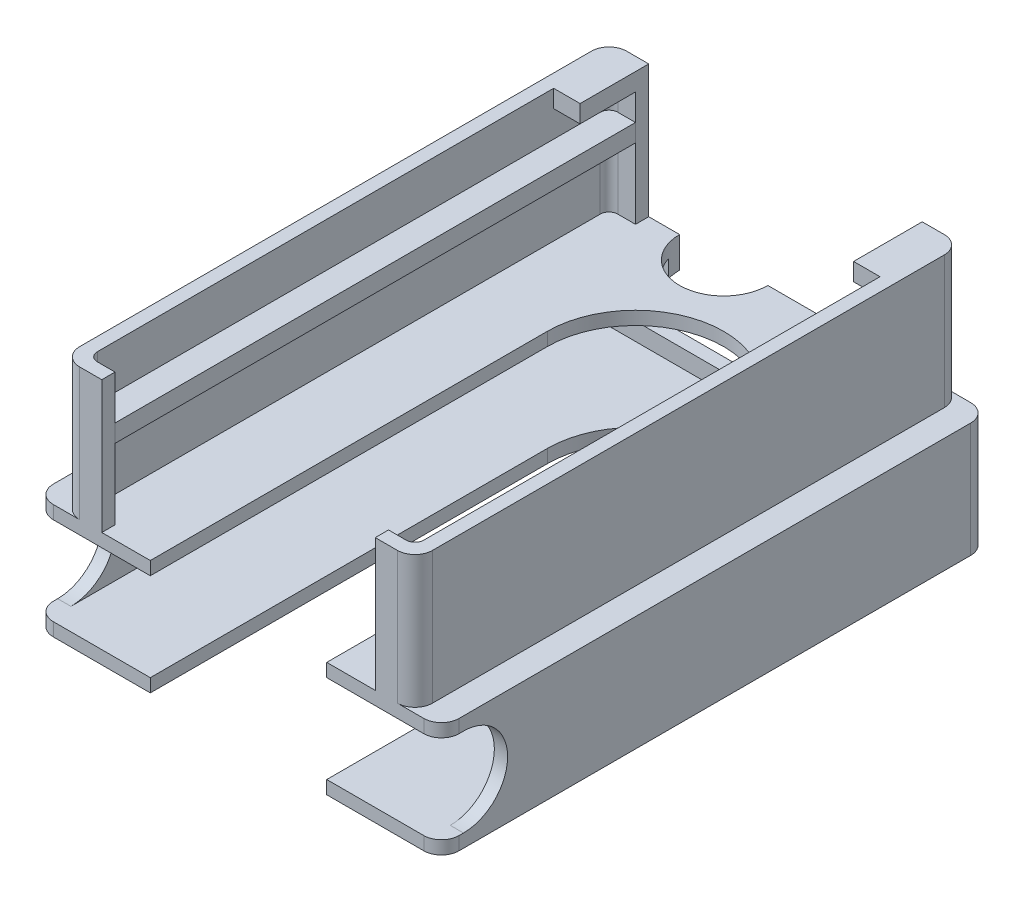
SolidWorks part; units mm, degrees
ref_plane "Front Plane" through (0, 0, 0) normal (0, 0, 1) x (1, 0, 0)
ref_plane "Top Plane" through (0, 0, 0) normal (0, 1, 0) x (1, 0, 0)
ref_plane "Right Plane" through (0, 0, 0) normal (1, 0, 0) x (0, 0, -1)
sketch "battery-base" plane through (0, 0, 0) normal (0, 1, 0) x (1, 0, 0)
  line L0 (-10.75, -13.5) -> (-11.5, -13.5)
  line L1 (-10.5, 16.25) -> (10.5, 16.25)
  line L2 (11.5, 15.25) -> (11.5, -13.75)
  line L3 (10.5, -14.75) -> (-10.5, -14.75)
  line L4 (-11.5, 15.25) -> (-11.5, -13.75)
  line L7 (10.25, 15.5) -> (-10.25, 15.5)
  line L8 (10.75, 15) -> (10.75, -13.5)
  line L9 (10.25, -14) -> (-10.25, -14)
  line L10 (-10.75, 15) -> (-10.75, -13.5)
  line L13 (10.75, -13.5) -> (11.5, -13.5)
  arc A0 (-11.5, -13.75) -> (-10.5, -14.75) centre (-10.5, -13.75) ccw
  arc A1 (11.5, -13.75) -> (10.5, -14.75) centre (10.5, -13.75) cw
  arc A2 (11.5, 15.25) -> (10.5, 16.25) centre (10.5, 15.25) ccw
  arc A3 (-11.5, 15.25) -> (-10.5, 16.25) centre (-10.5, 15.25) cw
  arc A4 (-10.75, 15) -> (-10.25, 15.5) centre (-10.25, 15) cw
  arc A5 (-10.75, -13.5) -> (-10.25, -14) centre (-10.25, -13.5) ccw
  arc A6 (10.25, -14) -> (10.75, -13.5) centre (10.25, -13.5) ccw
  arc A7 (10.75, 15) -> (10.25, 15.5) centre (10.25, 15) ccw
  point P0 (0, 0)
  point P6 (0, 0)
extrude "base-extrude" add sketch "battery-base" along normal blind 0.75 contours L3 A0 L4 A3 L1 A2 L2 A1
extrude "sidewall-extrude" add sketch "battery-base<12>" along normal blind 5.75 contours A7 L8 L13 L2 A2 L1 A3 L4 L0 L10 A4 L7 region at (-11.125, 0, 13.124)
sketch "battery-base<12>" plane through (0, 0, 0) normal (0, 1, 0) x (1, 0, 0) same geometry as "battery-base"
extrude "top-extrude" add sketch "battery-base<13>" along normal blind 0.75 from offset 5.75 contours L8 A7 L7 A4 L10 A5 L9 A6 | A6 L9 A5 L0 L4 A0 L3 A1 L2 L13 | A7 L8 L13 L2 A2 L1 A3 L4 L0 L10 A4 L7 region at (0, 0, 14.3418) region at (-11.125, 0, 13.124) region at (0, 0, -0.75)
sketch "battery-base<13>" plane through (0, 0, 0) normal (0, 1, 0) x (1, 0, 0) same geometry as "battery-base"
sketch "round-cut" plane through (11.5, 0, 0) normal (1, 0, 0) x (0, 0, -1)
  line L0 (-13.5, 5.75) -> (-13.5, 0.75) construction
  line L1 (-13.5, 5.75) -> (-13.75, 5.75) construction
  arc A0 (-13.5, 0.75) -> (-13.5, 5.75) centre (-13.5, 3.25) ccw
extrude "Cut-Extrude1" cut sketch "round-cut" against normal through all and the other way through all
sketch "PCB-support" plane through (0, 6.5, 0) normal (0, 1, 0) x (1, 0, 0)
  line L0 (-7.75, -14) -> (-7.75, 15.5)
  line L1 (-8.75, 15.5) -> (8.75, 15.5)
  line L2 (-9.25, 15) -> (-9.25, -13.5)
  line L3 (-8.75, -14) -> (8.75, -14)
  line L4 (9.25, 15) -> (9.25, -13.5)
  line L5 (-9, 16.25) -> (9, 16.25)
  line L6 (-10, 15.25) -> (-10, -13.75)
  line L7 (-9, -14.75) -> (9, -14.75)
  line L8 (10, 15.25) -> (10, -13.75)
  line L9 (7.75, -14) -> (7.75, 15.5)
  line L10 (-7.75, -14) -> (-7.75, -14.75)
  line L11 (7.75, -14) -> (7.75, -14.75)
  line L12 (-7.75, 15.5) -> (-7.75, 16.25)
  line L13 (7.75, 15.5) -> (7.75, 16.25)
  line L14 (-9.25, 12.3596) -> (-7.75, 12.3596)
  line L15 (-7.75, 12.3596) -> (7.75, 12.3596)
  line L16 (7.75, 12.3596) -> (9.25, 12.3596)
  arc A0 (-10, -13.75) -> (-9, -14.75) centre (-9, -13.75) ccw
  arc A1 (9, -14.75) -> (10, -13.75) centre (9, -13.75) ccw
  arc A2 (10, 15.25) -> (9, 16.25) centre (9, 15.25) ccw
  arc A3 (-9, 16.25) -> (-10, 15.25) centre (-9, 15.25) ccw
  arc A4 (-9.25, -13.5) -> (-8.75, -14) centre (-8.75, -13.5) ccw
  arc A5 (8.75, -14) -> (9.25, -13.5) centre (8.75, -13.5) ccw
  arc A6 (9.25, 15) -> (8.75, 15.5) centre (8.75, 15) ccw
  arc A7 (-8.75, 15.5) -> (-9.25, 15) centre (-8.75, 15) ccw
  line M4 (-10.5, -14.75) -> (10.5, -14.75)
  line M8 (10.5, 16.25) -> (-10.5, 16.25)
extrude "PCB-support-extrude" add sketch "PCB-support" along normal blind 1 from offset 4 contours L1 A7 L2 A4 L3 L0 | L4 A6 L1 L9 L3 A5 | L1 A7 L2 L14 L0 | L4 A6 L1 L9 L16 region at (-8.4991, 6.5, 0.8024) region at (-8.4926, 6.5, -13.913) region at (8.4991, 6.5, 0.8024) region at (8.4926, 6.5, -13.913)
extrude "PCB-rim-extrude" add sketch "PCB-support<3>" along normal blind 7.5 contours A7 L1 A6 L4 A5 L3 L11 A1 L8 A2 A3 L6 A0 L10 A4 L2 M4 M8 | A7 L1 L12 L5 A3 L6 A0 L10 L3 A4 L2 M4 region at (-9.5198, 6.5, -0.75) region at (9.5198, 6.5, -0.75)
sketch "PCB-support<3>" plane through (0, 6.5, 0) normal (0, 1, 0) x (1, 0, 0) same geometry as "PCB-support"
sketch "cut-away" plane through (0, 6.5, 0) normal (0, 1, 0) x (1, 0, 0)
  line L0 (-5, 7.75) -> (-5, -14.75)
  line L2 (5, 7.75) -> (5, -14.75)
  line L3 (5, -14.75) -> (-5, -14.75)
  line L4 (7.75, -14.75) -> (-7.75, -14.75) construction
  arc A0 (-5, 7.75) -> (5, 7.75) centre (0, 7.75) cw
extrude "Cut-Extrude2" cut sketch "cut-away" against normal through all
sketch "Sketch7" plane through (0, 0, -16.25) normal (0, 0, -1) x (-1, 0, 0)
  line L0 (8.5849, 3.25) -> (-8.5849, 3.25) construction
  line L1 (8.5849, 1.75) -> (-8.5849, 1.75)
  line L2 (8.5849, 4.75) -> (-8.5849, 4.75)
  arc A0 (8.5849, 1.75) -> (8.5849, 4.75) centre (8.5849, 3.25) ccw
  arc A1 (-8.5849, 4.75) -> (-8.5849, 1.75) centre (-8.5849, 3.25) ccw
  point P2 (0, 3.25)
extrude "Cut-Extrude3" cut sketch "Sketch7" against normal blind 3.5
sketch "Sketch8" plane through (0, 6.5, 0) normal (0, 1, 0) x (1, 0, 0)
  line L1 (-6, 16.25) -> (-1, 16.25)
  line L2 (-7.75, 16.25) -> (7.75, 16.25) construction
  arc A0 (-6, 16.25) -> (-1, 16.25) centre (-3.5, 16.25) ccw
extrude "Cut-Extrude4" cut sketch "Sketch8" against normal blind 2
extrude "Boss-Extrude1" add sketch "PCB-support<4>" along normal blind 1 from offset 6.5 contours L1 A7 L2 L14 L0 | L4 A6 L1 L9 L16 region at (-8.4926, 6.5, -13.913) region at (8.4926, 6.5, -13.913)
sketch "PCB-support<4>" plane through (0, 6.5, 0) normal (0, 1, 0) x (1, 0, 0) same geometry as "PCB-support"
